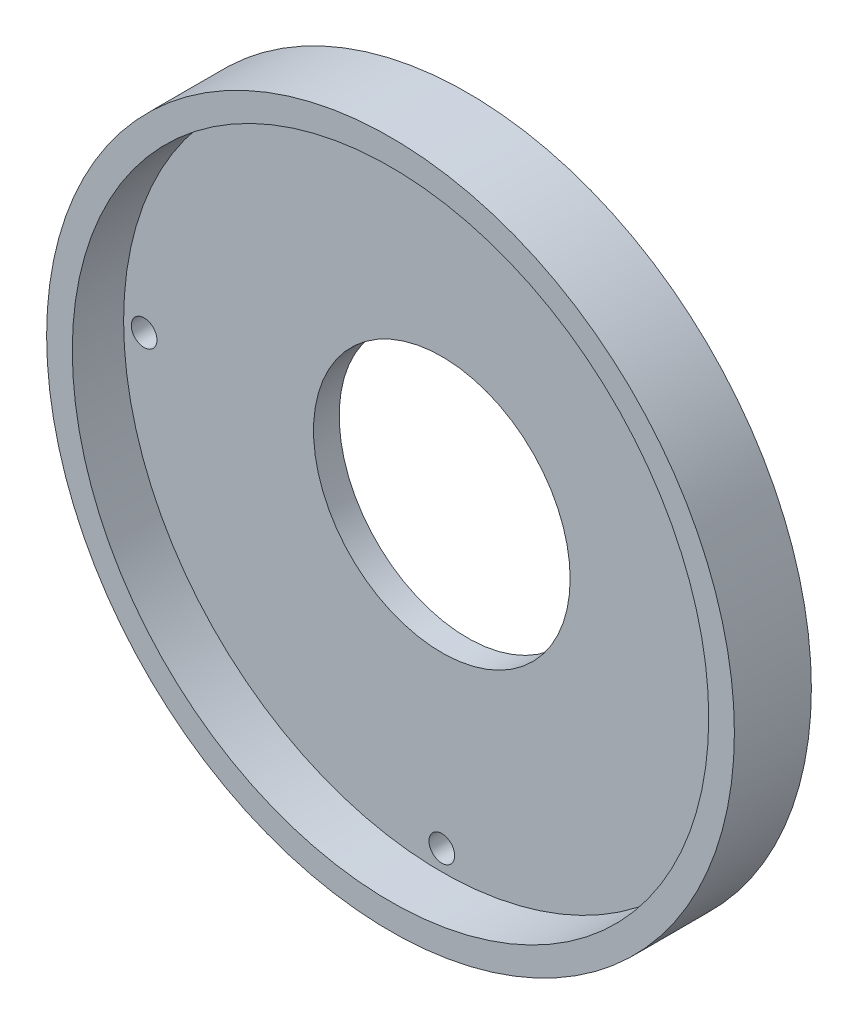
SolidWorks part; units mm, degrees
material "Glass"
ref_plane "Front Plane" through (0, 0, 0) normal (0, 0, 1) x (1, 0, 0)
ref_plane "Top Plane" through (0, 0, 0) normal (0, 1, 0) x (1, 0, 0)
ref_plane "Right Plane" through (0, 0, 0) normal (1, 0, 0) x (0, 0, -1)
sketch "Sketch1" plane through (0, 0, 0) normal (0, 0, 1) x (1, 0, 0)
  circle A0 centre (0, 0) radius 67
  circle A1 centre (0, 58) radius 2.5
  circle A2 centre (58, 0) radius 2.5
  circle A3 centre (0, -58) radius 2.5
  circle A4 centre (-58, 0) radius 2.5
  point P14 (0, 0)
  dimension "D1" = 4
  dimension "D2" = 58
extrude "Boss-Extrude1" add sketch "Sketch1" along normal blind 5
sketch "Sketch2" plane through (0, 0, 5) normal (0, 0, 1) x (1, 0, 0)
  circle A0 centre (-42.4264, -42.4264) radius 1.5
  circle A1 centre (42.4264, 42.4264) radius 1.5
  circle A2 centre (-38.8909, 38.8909) radius 1.5
  circle A3 centre (38.8909, -38.8909) radius 1.5
  point P8 (0, 0)
  point P9 (0, 0)
  point P10 (0, 0)
  dimension "D1" = 3
  dimension "D2" = 3
  dimension "D3" = 55
  dimension "D4" = 60
  dimension "D5" = 60
sketch "Sketch3" plane through (0, 0, 5) normal (0, 0, 1) x (1, 0, 0)
  circle A0 centre (0, 0) radius 25
extrude "Cut-Extrude1" cut sketch "Sketch3" against normal blind 10
sketch "Sketch4" plane through (0, 0, 5) normal (0, 0, 1) x (1, 0, 0)
  circle A0 centre (0, 0) radius 67
  circle A1 centre (0, 0) radius 62
extrude "Boss-Extrude2" add sketch "Sketch4" along normal blind 10
ref_plane "Plane1" through (0, 0, 0) normal (-0.7071, 0.7071, 0) x (0.7071, 0.7071, 0)
sketch "Sketch7" plane through (0, 0, 0) normal (-0.7071, 0.7071, 0) x (0.7071, 0.7071, 0)
  line L0 (-67, -15) -> (67, -15) construction
  circle A0 centre (0, -10) radius 1.25
  dimension "D1" = 5
  dimension "D2" = 2.5
extrude "Cut-Extrude4" cut sketch "Sketch7" against normal blind 121 and the other way blind 121
